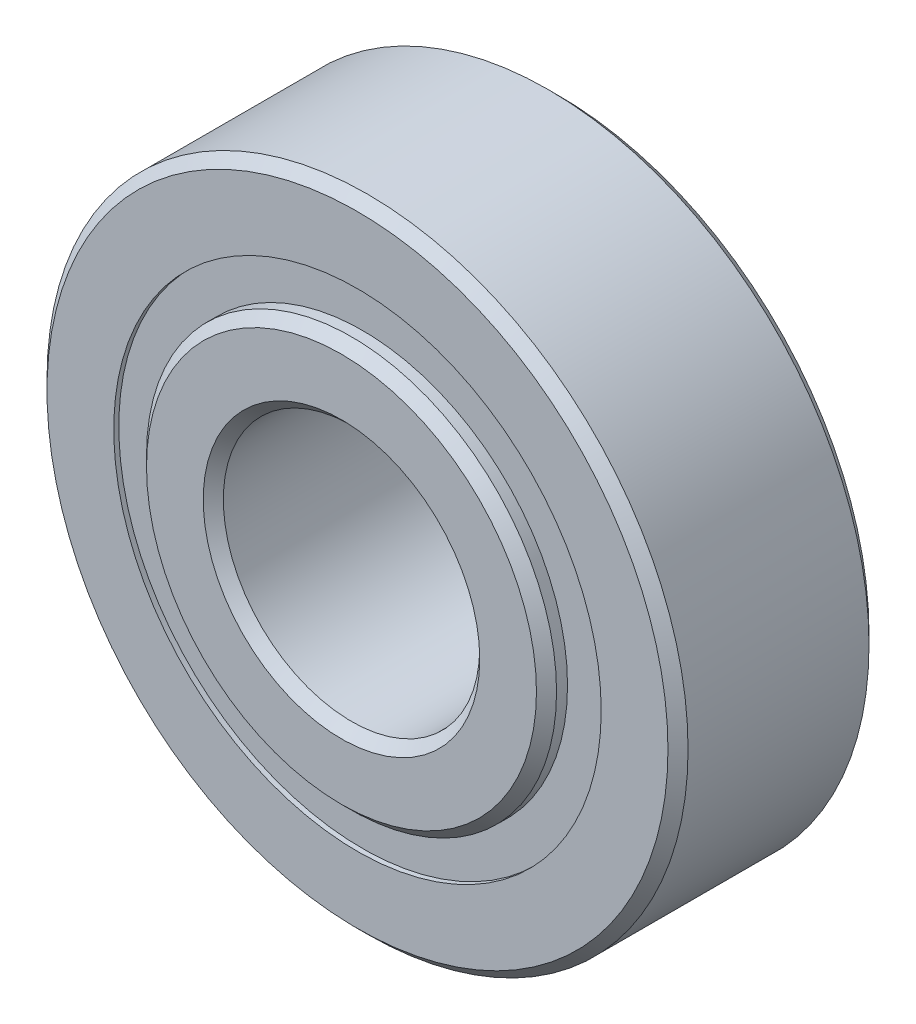
SolidWorks part; units mm, degrees
material "Cast Alloy Steel"
ref_plane "Front Plane" through (0, 0, 0) normal (0, 0, 1) x (1, 0, 0)
ref_plane "Top Plane" through (0, 0, 0) normal (0, 1, 0) x (1, 0, 0)
ref_plane "Right Plane" through (0, 0, 0) normal (1, 0, 0) x (0, 0, -1)
sketch "Sketch1" plane through (0, 0, 0) normal (1, 0, 0) x (0, 0, -1)
  line L0 (-2.4892, 0) -> (2.4892, 0) construction
  line L1 (0, 7.9375) -> (0, -7.9375) construction
  line L2 (2.2403, 7.9375) -> (-2.2403, 7.9375)
  line L3 (-2.2403, 7.9375) -> (-2.4892, 7.6886)
  line L4 (-2.4892, 7.6886) -> (-2.4892, 6.0352)
  line L5 (-2.4892, 6.0352) -> (-1.1063, 6.0352)
  line L6 (2.4892, 6.0352) -> (1.1063, 6.0352)
  line L7 (2.4892, 7.6886) -> (2.4892, 6.0352)
  line L8 (2.2403, 7.9375) -> (2.4892, 7.6886)
  line L9 (0, 7.9375) -> (0, 5.5563) construction
  line L10 (0, 5.5563) -> (0, 3.175) construction
  arc A0 (-1.1063, 6.0352) -> (1.1063, 6.0352) centre (0, 5.5563) cw
  point P14 (0, 3.175)
  dimension "D3" = 2.2126
  dimension "D1" = 45
  dimension "Width" = 4.9784
  dimension "OD" = 15.875
  dimension "D2" = 0.2489
  dimension "Shaft Dia" = 6.35
  dimension "D4" = 0.479
revolve "Revolve1" add sketch "Sketch1" angle 360 about L0
sketch "Sketch3" plane through (0, 0, 0) normal (1, 0, 0) x (0, 0, -1)
  line L0 (-1.1063, 5.0773) -> (-2.8854, 5.0773) construction
  line L1 (-2.4892, 7.6886) -> (-2.4892, 6.0352) construction
  line L2 (-2.2403, 7.9375) -> (-2.4892, 7.6886) construction
  line L3 (-2.8854, 5.0773) -> (-2.8854, 3.4239) construction
  line L4 (-2.8854, 3.4239) -> (-2.8854, 4.8284)
  line L5 (-2.8854, 3.4239) -> (-2.6365, 3.175)
  line L6 (-2.6365, 3.175) -> (2.6365, 3.175)
  line L8 (2.6365, 3.175) -> (2.8854, 3.4239)
  line L10 (2.8854, 3.4239) -> (2.8854, 5.0773) construction
  line L11 (2.8854, 5.0773) -> (1.1063, 5.0773) construction
  line L12 (0, 7.9375) -> (0, -7.9375) construction
  line L13 (2.2403, 7.9375) -> (2.4892, 7.6886) construction
  line L14 (-2.8854, 4.8284) -> (-2.6365, 5.0773)
  line L15 (-2.6365, 5.0773) -> (-1.1063, 5.0773)
  line L16 (1.1063, 5.0773) -> (2.6365, 5.0773)
  line L17 (2.6365, 5.0773) -> (2.8854, 4.8284)
  line L18 (2.8854, 4.8284) -> (2.8854, 3.4239)
  arc A1 (1.1063, 5.0773) -> (-1.1063, 5.0773) centre (0, 5.5562) cw
  arc A2 (1.1063, 6.0352) -> (-1.1063, 6.0352) centre (0, 5.5563) ccw construction
  dimension "D1" = 45
  dimension "Ring" = 5.7709
revolve "Revolve3" add sketch "Sketch3" angle 360 about L0
sketch "Sketch4" plane through (0, 0, 0) normal (1, 0, 0) x (0, 0, -1)
  line L0 (-1.2055, 5.5563) -> (1.2055, 5.5563)
  arc A2 (-1.2055, 5.5563) -> (1.2055, 5.5563) centre (0, 5.5563) cw
  arc A3 (1.1063, 6.0352) -> (-1.1063, 6.0352) centre (0, 5.5563) ccw construction
revolve "Revolve4" add sketch "Sketch4" angle 360 about L0
ref_axis "Axis1" through (0, 0, -2.4892) along (0, 0, 1)
pattern_circular "CirPattern1" count 12 every 30 about axis through (0, 0, -2.4892) along (0, 0, 1) of bodies 104
sketch "Sketch5" plane through (0, 0, 0) normal (1, 0, 0) x (0, 0, -1)
  line L0 (-2.4892, 6.0352) -> (-1.1063, 6.0352) construction
  line L1 (-2.3647, 6.0352) -> (-1.2055, 6.0352)
  line L2 (-2.3647, 6.0352) -> (-2.3647, 5.0773)
  line L3 (-2.3647, 5.0773) -> (-1.2055, 5.0773)
  line L4 (-1.2055, 6.0352) -> (-1.2055, 5.0773)
  line L5 (-1.1063, 5.0773) -> (-2.8854, 5.0773) construction
  line L6 (2.4892, 6.0352) -> (1.1063, 6.0352) construction
  line L7 (2.3647, 6.0352) -> (1.2055, 6.0352)
  line L8 (2.3647, 6.0352) -> (2.3647, 5.0773)
  line L9 (2.3647, 5.0773) -> (1.2055, 5.0773)
  line L10 (1.2055, 6.0352) -> (1.2055, 5.0773)
  line L11 (2.8854, 5.0773) -> (1.1063, 5.0773) construction
  line L12 (-2.2403, 7.9375) -> (-2.4892, 7.6886) construction
  point P18 (-2.3647, 7.813)
revolve "Revolve5" add sketch "Sketch5" angle 360 about L0
equation "\"D2@Sketch1\" = \"Width@Sketch1\"*.05"
equation "\"D3@Sketch1\" = \"Width@Sketch1\"/2.25"
equation "\"D4@Sketch1\" = (((\"OD@Sketch1\"-\"Width@Sketch1\")/2)/3.25)/3.5"
equation "\"D2@CirPattern1\" = 360/\"Balls@CirPattern1\""
